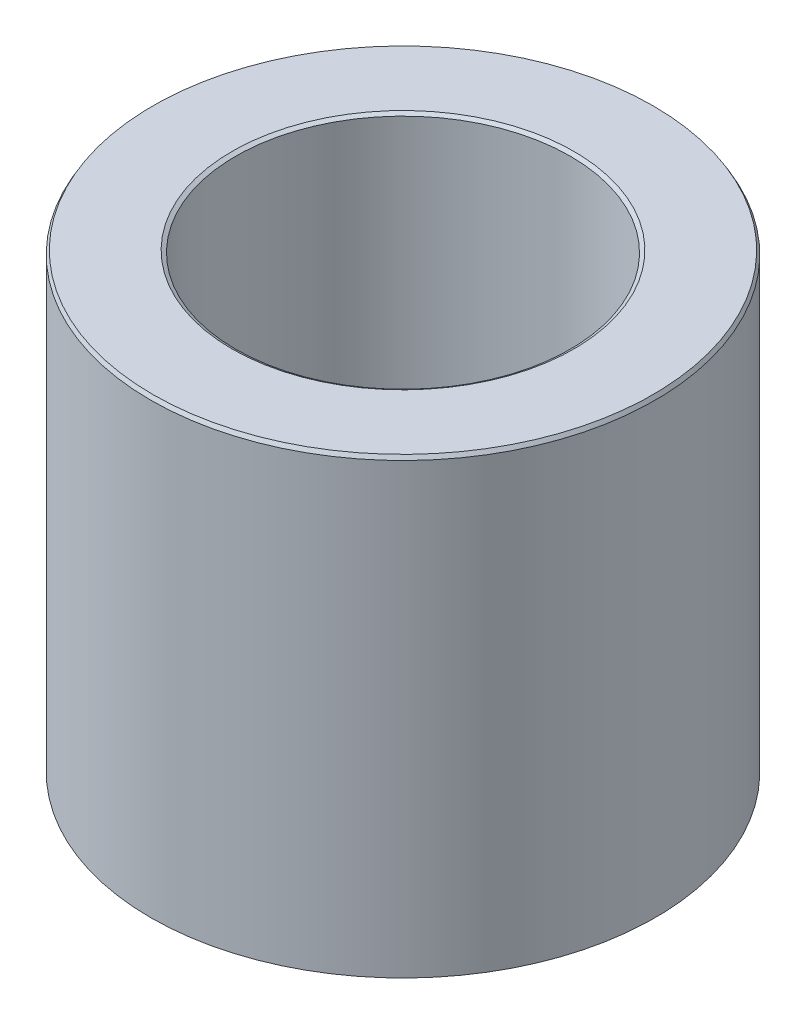
SolidWorks part; units mm, degrees
ref_plane "Front Plane" through (0, 0, 0) normal (0, 0, 1) x (1, 0, 0)
ref_plane "Top Plane" through (0, 0, 0) normal (0, 1, 0) x (1, 0, 0)
ref_plane "Right Plane" through (0, 0, 0) normal (1, 0, 0) x (0, 0, -1)
sketch "Sketch1" plane through (0, 0, 0) normal (0, 1, 0) x (1, 0, 0)
  circle A0 centre (0, 0) radius 45
  dimension "SLEEVE_OD" = 90
extrude "Boss-Extrude1" add sketch "Sketch1" along normal blind 81.0057
sketch "Sketch2" plane through (0, 0, 0) normal (0, 1, 0) x (1, 0, 0)
  circle A0 centre (0, 0) radius 29.8366
  dimension "BORE_D" = 59.6731
extrude "Cut-Extrude1" cut sketch "Sketch2" along normal through all
chamfer "Chamfer1" distance 0.6743 angle 30 4 edges at (0, 81.0057, 29.8366) (0, 0, 29.8366) (0, 0, 45) (0, 81.0057, 45) first distance on face at (0, 81.0057, 29.8366) first distance on face at (0, 0, 29.8366) first distance on face at (0, 81.0057, 45)
